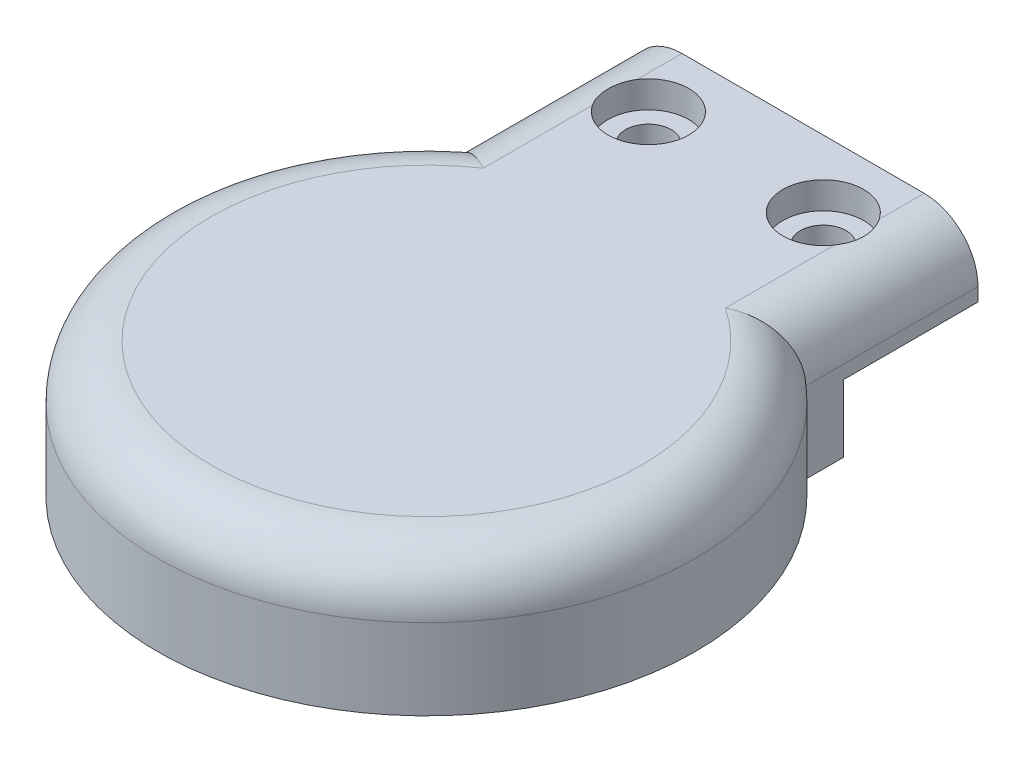
SolidWorks part; units mm, degrees
ref_plane "前视基准面" through (0, 0, 0) normal (0, 0, 1) x (1, 0, 0)
ref_plane "上视基准面" through (0, 0, 0) normal (0, 1, 0) x (1, 0, 0)
ref_plane "右视基准面" through (0, 0, 0) normal (1, 0, 0) x (0, 0, -1)
sketch "草图1" plane through (0, 0, 0) normal (0, 0, 1) x (1, 0, 0)
  line L9 (6.5, -6.2249) -> (6.5, -10.6)
  line L10 (-6.5, -10.6) -> (-6.5, -6.2249)
  line L11 (6.5, -10.6) -> (-6.5, -10.6)
  line L12 (6.5, 10.6) -> (6.5, 6.2249)
  line L16 (-6.5, 10.6) -> (-6.5, 6.2249)
  line L17 (6.5, 10.6) -> (-6.5, 10.6)
  arc A9 (-6.5, 6.2249) -> (-6.5, -6.2249) centre (0, 0) ccw
  arc A10 (6.5, -6.2249) -> (6.5, 6.2249) centre (0, 0) ccw
  dimension "D1" = 21.2
sketch "草图3" plane through (0, 0, 0) normal (0, 1, 0) x (1, 0, 0)
  line L0 (-6.5, -8.9007) -> (-6.5, -7.5)
  line L1 (6.5, -2.5) -> (-6.5, -2.5)
  line L2 (-6.5, -7.5) -> (6.5, -7.5)
  line L3 (-6.5, -2.5) -> (-6.5, -7.5)
  line L4 (6.5, 0) -> (-6.5, 0)
  line L8 (-6.5, 0) -> (-6.5, -2.5)
  line L9 (6.5, -8.9007) -> (6.5, -7.5)
  line L10 (6.5, -7.5) -> (6.5, -2.5)
  line L11 (6.5, 0) -> (6.5, -2.5)
  arc A1 (-6.5, -8.9007) -> (6.5, -8.9007) centre (0, -16.5) ccw
  circle A2 centre (0, -16.5) radius 6.1
  circle A3 centre (3.25, -5) radius 0.85
  circle A4 centre (3.25, -5) radius 1.5
  circle A5 centre (-3.25, -5) radius 0.85
  circle A6 centre (-3.25, -5) radius 1.5
extrude "凸台-拉伸1" add sketch "草图3" along normal blind 5 contours L0 L2 L9 A1 | A2
extrude "凸台-拉伸2" add sketch "草图3<5>" along normal blind 5 contours L1 L3 L2 L10
sketch "草图3<5>" plane through (0, 0, 0) normal (0, 1, 0) x (1, 0, 0) same geometry as "草图3"
extrude "切除-拉伸1" cut sketch "草图3<6>" along normal blind 2.5 contours L2 L10 L1 L3
sketch "草图3<6>" plane through (0, 0, 0) normal (0, 1, 0) x (1, 0, 0) same geometry as "草图3"
extrude "切除-拉伸2" cut sketch "草图3<7>" along normal blind 7.5 contours A3 | A5
sketch "草图3<7>" plane through (0, 0, 0) normal (0, 1, 0) x (1, 0, 0) same geometry as "草图3"
extrude "切除-拉伸3" cut sketch "草图3<8>" against normal blind 1 from surface contours A6 | A4 starting at face at (0, 5, 22.6)
sketch "草图3<8>" plane through (0, 0, 0) normal (0, 1, 0) x (1, 0, 0) same geometry as "草图3"
extrude "凸台-拉伸3" add sketch "草图3<9>" along normal blind 5 contours A2
sketch "草图3<9>" plane through (0, 0, 0) normal (0, 1, 0) x (1, 0, 0) same geometry as "草图3"
extrude "切除-拉伸4" cut sketch "草图3<10>" along normal blind 3.5 contours A2
sketch "草图3<10>" plane through (0, 0, 0) normal (0, 1, 0) x (1, 0, 0) same geometry as "草图3"
fillet "圆角1" radius 2 1 edges at (0, 5, 26.5)
fillet "圆角2" radius 2 2 edges at (6.5, 5, 7.1682) (-6.5, 5, 7.1682)
